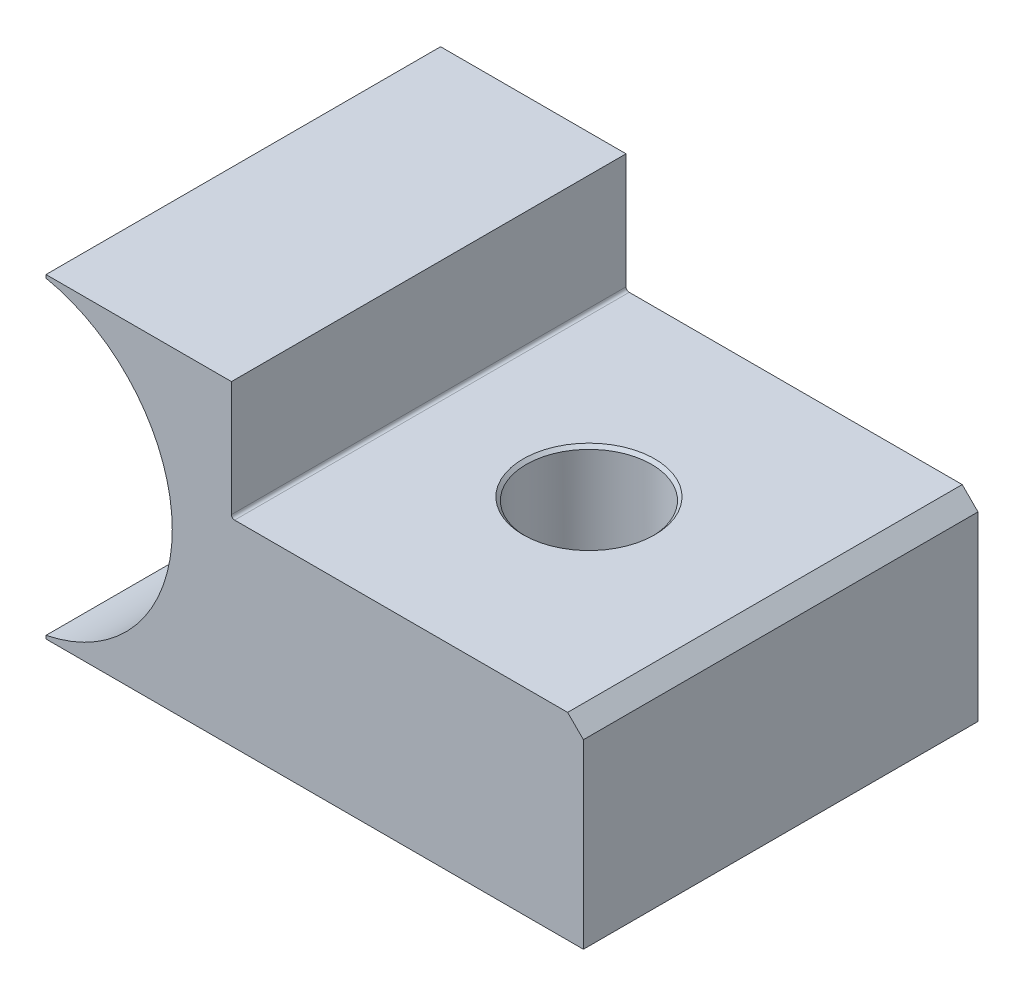
SolidWorks part; units mm, degrees
material "AISI Type A2 Tool Steel Custom"
ref_plane "Front Plane" through (0, 0, 0) normal (0, 0, 1) x (1, 0, 0)
ref_plane "Top Plane" through (0, 0, 0) normal (0, 1, 0) x (1, 0, 0)
ref_plane "Right Plane" through (0, 0, 0) normal (1, 0, 0) x (0, 0, -1)
sketch "Sketch1" plane through (0, 0, 0) normal (0, 0, 1) x (1, 0, 0)
  line L1 (2.54, 0) -> (45.7835, 0)
  line L3 (2.54, 25.4) -> (17.4625, 25.4)
  line L4 (45.7835, 0) -> (45.7835, 15.875)
  line L5 (2.54, 25.4) -> (2.54, 25.1434)
  line L6 (17.4625, 25.4) -> (17.4625, 15.875)
  line L7 (17.4625, 15.875) -> (45.7835, 15.875)
  line L8 (2.54, 0.2566) -> (2.54, 0)
  arc A1 (2.54, 0.2566) -> (2.54, 25.1434) centre (0, 12.7) ccw
  dimension "D2" = 25.4
  dimension "D1" = 14.9225
  dimension "D3" = 9.525
  dimension "D4" = 2.54
  dimension "D5" = 28.321
  dimension "D6" = 15.875
  dimension "D7" = 0.2566
extrude "Boss-Extrude1" add sketch "Sketch1" along normal blind 31.75
sketch "Sketch5" plane through (0, 15.875, 0) normal (0, 1, 0) x (1, 0, 0)
  line L0 (0, -31.75) -> (0, 0) construction
  line L1 (2.54, -31.75) -> (2.54, 0) construction
  point P0 (30.353, -15.875)
  point P5 (0, -15.875)
  point P8 (2.54, -15.875)
  dimension "D1" = 30.353
hole_wizard "X (0.397) Diameter Hole1" positions "Sketch5" profile "Sketch4" hole size "X" standard "ANSI Inch" end condition through all
sketch "Sketch4" plane through (30.353, 15.875, 15.875) normal (1, 0, 0) x (0, 0, 1)
  line L0 (0, 0) -> (0, 15.875)
  line L1 (0, 15.875) -> (5.0419, 15.875)
  line L2 (5.0419, 15.875) -> (5.0419, 0)
  line L5 (5.0419, 0) -> (0, 0)
  line L11 (0, -6.35) -> (0, 107.95) construction
  dimension "Thru Hole Dia." = 10.0838
  dimension "Thru Hole Depth" = 15.875
chamfer "Chamfer1" distance 1.27 angle 45 1 edges at (45.7835, 15.875, 15.875)
chamfer "Chamfer2" distance 0.254 angle 45 1 edges at (30.353, 15.875, 20.9169)
fillet "Fillet1" radius 0.254 1 edges at (17.4625, 15.875, 15.875)
